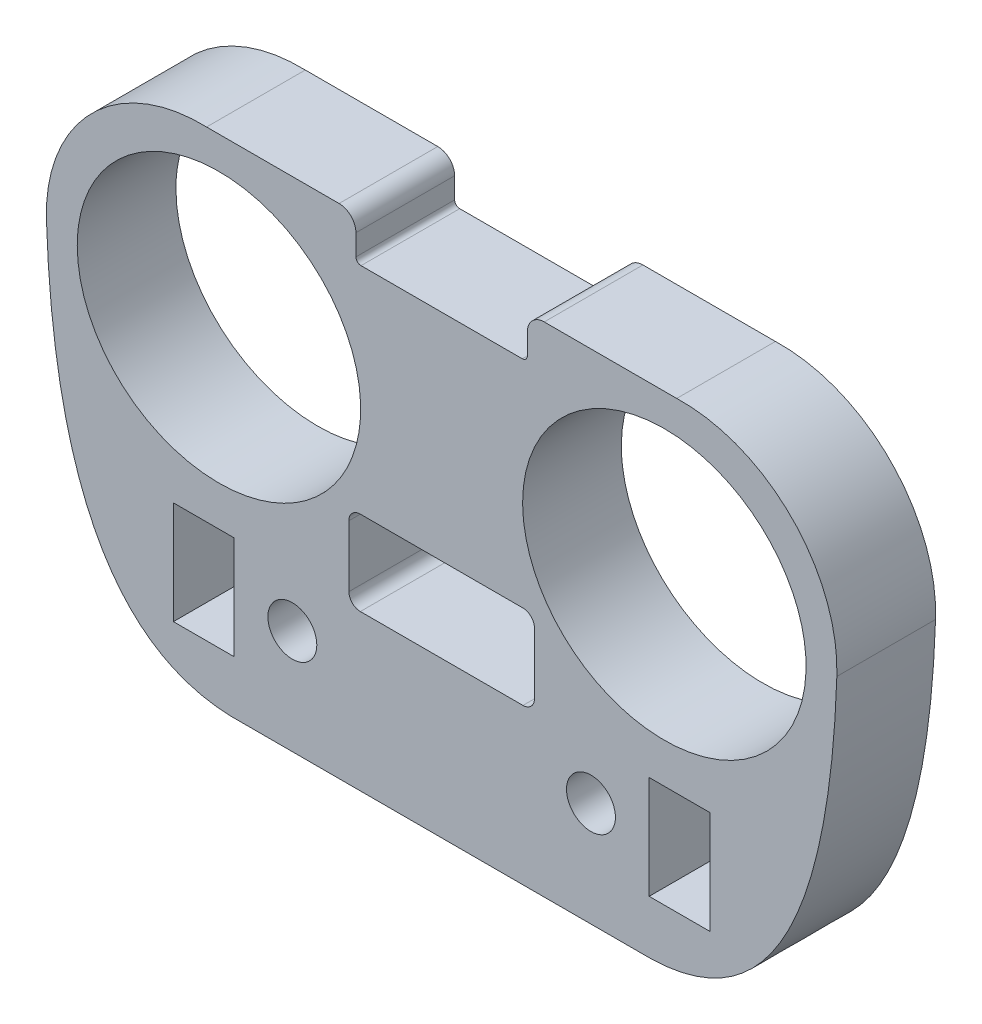
SolidWorks part; units mm, degrees
material "Acrylic (Medium-high impact)"
ref_plane "Front Plane" through (0, 0, 0) normal (0, 0, 1) x (1, 0, 0)
ref_plane "Top Plane" through (0, 0, 0) normal (0, 1, 0) x (1, 0, 0)
ref_plane "Right Plane" through (0, 0, 0) normal (1, 0, 0) x (0, 0, -1)
sketch "Model" plane through (0, 0, 0) normal (0, 0, 1) x (1, 0, 0)
  line L0 (549.8561, 574.3347) -> (554.6761, 574.3347)
  line L1 (554.6761, 576.8347) -> (549.1761, 576.8347) construction
  line L2 (554.6761, 576.8347) -> (560.1761, 576.8347) construction
  line L3 (554.6761, -405.4445) -> (554.6761, 49594.5555) construction
  line L4 (540.7427, 594.6497) -> (549.5961, 594.6497)
  line L5 (542.1922, 565.1247) -> (567.16, 565.1247)
  line L6 (549.8561, 579.3347) -> (554.6761, 579.3347)
  line L7 (566.9761, 574.3747) -> (566.9761, 568.2747)
  line L8 (570.5761, 574.3747) -> (566.9761, 574.3747)
  line L9 (570.5761, 568.2747) -> (570.5761, 574.3747)
  line L10 (566.9761, 568.2747) -> (570.5761, 568.2747)
  line L11 (560.1761, 578.6547) -> (560.1761, 575.0147)
  line L12 (559.4961, 579.3347) -> (554.6761, 579.3347)
  line L13 (559.4961, 574.3347) -> (554.6761, 574.3347)
  line L14 (538.7761, 571.3247) -> (570.5761, 571.3247) construction
  line L15 (541.4761, 584.7347) -> (567.8761, 584.7347) construction
  line L16 (549.5961, 592.1097) -> (559.7561, 592.1097)
  line L17 (549.5961, 592.1097) -> (549.5961, 594.6497)
  line L18 (559.7561, 592.1097) -> (559.7561, 594.6497)
  line L19 (559.7561, 594.6497) -> (568.6095, 594.6497)
  line L20 (541.4761, 584.7347) -> (541.4761, 592.7347) construction
  line L21 (549.1761, 578.6547) -> (549.1761, 575.0147)
  line L32 (542.3761, 568.2747) -> (538.7761, 568.2747)
  line L33 (538.7761, 568.2747) -> (538.7761, 574.3747)
  line L34 (538.7761, 574.3747) -> (542.3761, 574.3747)
  line L35 (542.3761, 574.3747) -> (542.3761, 568.2747)
  circle A0 centre (545.8261, 571.3247) radius 1.45
  arc A1 (578.1008, 585.1247) -> (568.6095, 594.6497) centre (568.8929, 585.4407) ccw
  arc A3 (549.1761, 575.0147) -> (549.8561, 574.3347) centre (549.8561, 575.0147) ccw
  arc A4 (549.1761, 578.6547) -> (549.8561, 579.3347) centre (549.8561, 578.6547) cw
  arc A5 (560.1761, 578.6547) -> (559.4961, 579.3347) centre (559.4961, 578.6547) ccw
  arc A6 (560.1761, 575.0147) -> (559.4961, 574.3347) centre (559.4961, 575.0147) cw
  arc A7 (531.2514, 585.1247) -> (540.7427, 594.6497) centre (540.4593, 585.4407) cw
  circle A9 centre (563.5261, 571.3247) radius 1.45
  ellipse E0 centre (541.4761, 584.7347) end of major axis (533.0761, 584.7347) minor radius 8
  ellipse E1 centre (567.8761, 584.7347) end of major axis (559.4761, 584.7347) minor radius 8
  spline S0 degree 2 poles (578.1008, 585.1247) (577.4253, 565.4445) (567.16, 565.1247) knots 0 0 0 1 1 1
  spline S48 degree 2 poles (531.2514, 585.1247) (531.9269, 565.4445) (542.1922, 565.1247) knots 0 0 0 1 1 1
  point P0 (554.6761, 571.3247)
  point P2 (541.4761, 592.7347)
  point P19 (549.8761, 584.7347)
  point P32 (559.4761, 584.7347)
  point P33 (554.6761, 584.7347)
  point P34 (554.6761, 565.1247)
  point P36 (554.6761, 576.8347)
  point P40 (554.6761, 592.1097)
  dimension "D11" = 2.9
  dimension "D12" = 8
  dimension "D14" = 0.68
  dimension "D16" = 10.16
  dimension "D1" = 3.45
  dimension "D2" = 8.85
  dimension "D3" = 20
  dimension "D4" = 6.1
  dimension "D5" = 11
  dimension "D6" = 5
  dimension "D7" = 3.6
  dimension "D8" = 29.525
  dimension "D9" = 6.2
  dimension "D10" = 0.04
  dimension "D13" = 13.2
  dimension "D15" = 7.9
  dimension "D17" = 2.54
  dimension "D18" = 5.51
  dimension "D19" = 8.4
extrude "Boss-Extrude1" add sketch "Model" along normal blind 5.85 contours A7 S48 L5 S0 A1 L4 A9 L11 A6 L13 L0 A3 L21 A4 L6 L12 A5 E0 A0 L10 L7 L8 L9 L34 L35 L32 L33 E1 region at (545.1694, 594.0958, 0)
fillet "Fillet1" radius 0.3 2 edges at (559.7561, 592.1097, 2.925) (549.5961, 592.1097, 2.925)
fillet "Fillet2" radius 1 2 edges at (559.7561, 594.6497, 2.925) (549.5961, 594.6497, 2.925)
